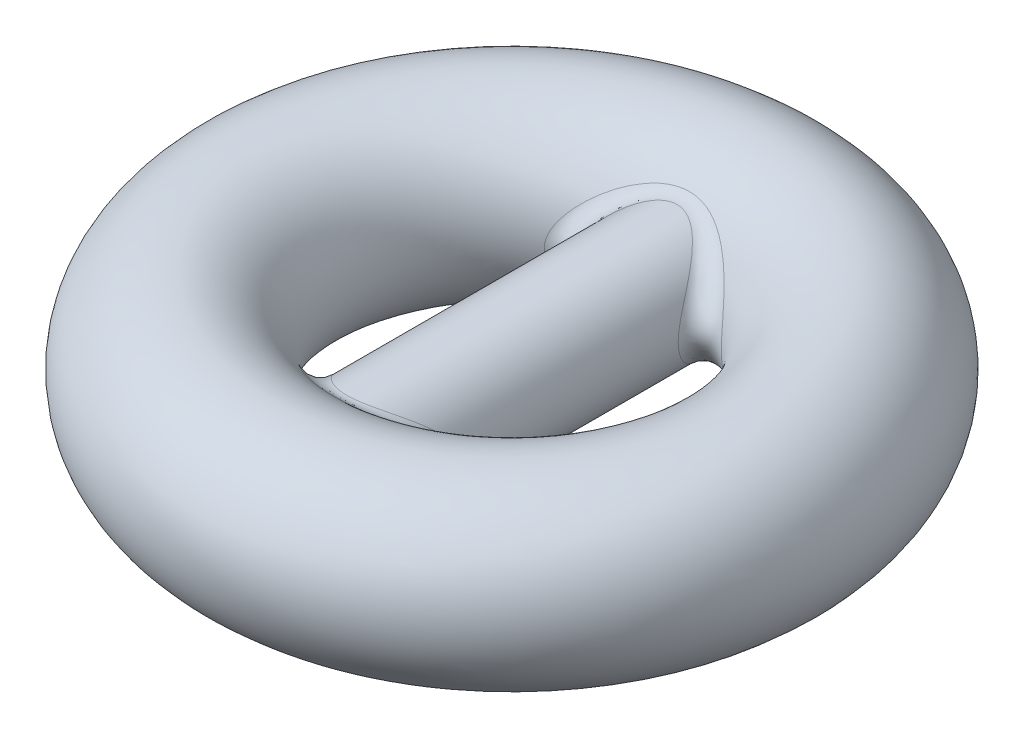
SolidWorks part; units mm, degrees
ref_plane "Front Plane" through (0, 0, 0) normal (0, 0, 1) x (1, 0, 0)
ref_plane "Top Plane" through (0, 0, 0) normal (0, 1, 0) x (1, 0, 0)
ref_plane "Right Plane" through (0, 0, 0) normal (1, 0, 0) x (0, 0, -1)
sketch "Sketch1" plane through (0, 0, 0) normal (0, 0, 1) x (1, 0, 0)
  circle A0 centre (0, 0) radius 10
  dimension "D1" = 20
extrude "Boss-Extrude1" add sketch "Sketch1" along normal blind 60
sketch "Sketch2" plane through (0, 0, 0) normal (1, 0, 0) x (0, 0, -1)
  line L0 (-30, 10) -> (-30, 25.6158) construction
  line L1 (0, 10) -> (-60, 10) construction
  circle A0 centre (10, 0) radius 15
  dimension "D2" = 30
  dimension "D1" = 10
revolve "Revolve1" add sketch "Sketch2" angle 360 about L0
fillet "Fillet1" radius 3 2 edges at (5.1646, 8.5631, 2.8016) (9.1108, 4.1224, 53.8999)
equation "\"dia_ring\"=30"
equation "\"D2@Sketch2\"=\"dia_ring\""
equation "\"center_length\"=60"
equation "\"D1@Boss-Extrude1\"=\"center_length\""
